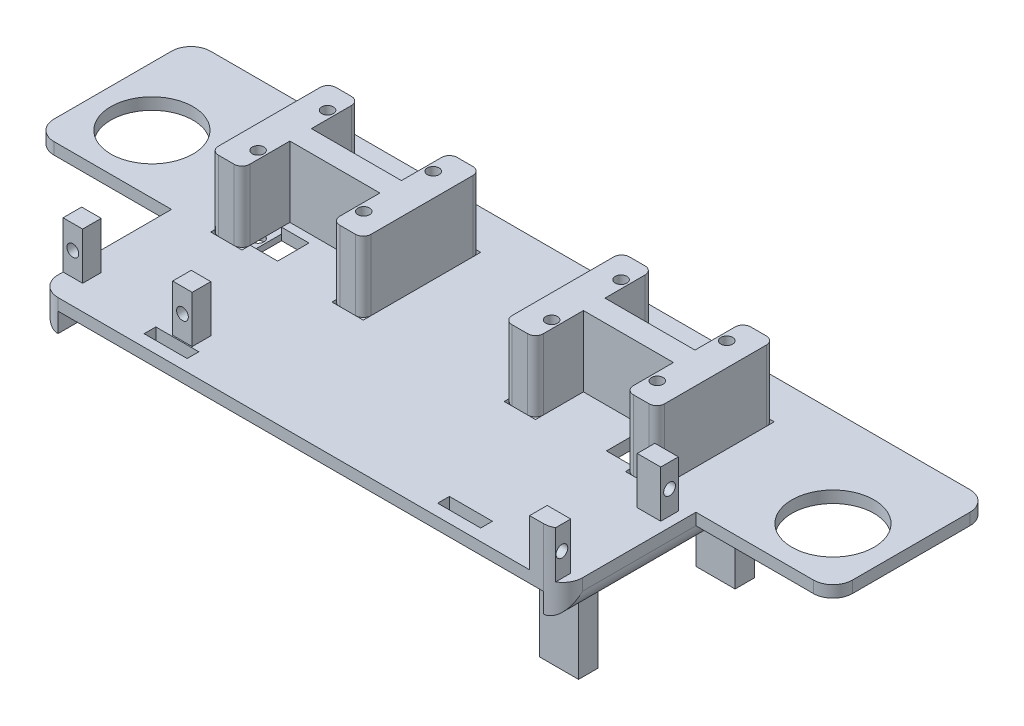
SolidWorks part; units mm, degrees
other "HMount1"
other "Controller Base"
other "HMount2"
ref_plane "Front Plane" through (0, 0, 0) normal (0, 0, 1) x (1, 0, 0)
ref_plane "Top Plane" through (0, 0, 0) normal (0, 1, 0) x (1, 0, 0)
ref_plane "Right Plane" through (0, 0, 0) normal (1, 0, 0) x (0, 0, -1)
sketch "Sketch1" plane through (0, 0, 0) normal (1, 0, 0) x (0, 0, -1)
  line L0 (0, 0) -> (0, 30)
  line L1 (0, 30) -> (45, 30)
  line L2 (45, 30) -> (45, 0)
  line L3 (45, 0) -> (40, 0)
  line L4 (40, 0) -> (40, 27)
  line L5 (40, 27) -> (5, 27)
  line L6 (5, 27) -> (5, 0)
  line L7 (5, 0) -> (0, 0)
  dimension "D1" = 5
  dimension "D2" = 5
  dimension "D3" = 3
  dimension "D4" = 35
  dimension "D5" = 30
extrude "C Bracket" add sketch "Sketch1" along normal blind 10
sketch "Sketch3" plane through (0, 30, 0) normal (0, 1, 0) x (1, 0, 0)
  line L0 (10, 45) -> (10, 0) construction
  line L1 (-113, -15) -> (21, -15)
  line L2 (-113, -15) -> (-113, 59)
  line L3 (-113, 59) -> (21, 59)
  line L4 (21, -15) -> (21, 59)
  line L5 (10, 0) -> (0, 0) construction
  line L6 (-148, 19) -> (-148, 59)
  line L7 (-113, 59) -> (-148, 59)
  line L8 (-46, 59) -> (-46, -15) construction
  line L9 (-113, 19) -> (-113, 59)
  line L10 (21, 19) -> (56, 19)
  line L11 (21, 19) -> (21, 59)
  line L12 (21, 59) -> (56, 59)
  line L13 (56, 19) -> (56, 59)
  line L14 (-113, 19) -> (-148, 19)
  line L15 (-113, -15) -> (-113, 59)
  circle A0 centre (41, 34) radius 10.5
  circle A1 centre (-133, 34) radius 10.5
  line M10 (0, 45) -> (0, 0)
  line M11 (0, 0) -> (10, 0)
  line M12 (10, 0) -> (10, 45)
  line M13 (10, 45) -> (0, 45)
  dimension "D9" = 21
  dimension "D1" = 74
  dimension "D2" = 134
  dimension "D3" = 11
  dimension "D4" = 15
  dimension "D5" = 25
  dimension "D6" = 20
  dimension "D7" = 35
  dimension "D8" = 40
extrude "Main Body" add sketch "Sketch3" along normal blind 3 separate body contours L8 L3 L2 L1 | L14 L2 L7 L6 A1 | L3 L8 L1 L4 M10 M13 M12 M11 | L10 L13 L12 L4 A0 | L2 L1 L4 L3 region at (-79.5, 30, -22) region at (-14.2469, 30, -21.9501) region at (-130.5, 30, -19.5315) region at (21.5315, 30, -39)
sketch "Sketch4" plane through (0, 30, 0) normal (0, -1, 0) x (1, 0, 0)
  line L0 (-148, -59) -> (56, -59) construction
  line L1 (-113, 15) -> (-108, 15)
  line L2 (-113, 15) -> (-113, -59)
  line L3 (-113, -59) -> (-108, -59)
  line L4 (-108, 15) -> (-108, -59)
  line L5 (-46, 15) -> (-46, -59) construction
  line L6 (-113, 15) -> (21, 15) construction
  line L7 (16, 15) -> (16, -59)
  line L8 (21, -59) -> (16, -59)
  line L9 (21, 15) -> (21, -59)
  line L10 (21, 15) -> (16, 15)
  dimension "D1" = 5
extrude "Boss-Extrude4" add sketch "Sketch4" along normal blind 5
sketch "Sketch6" plane through (0, 30, 0) normal (0, -1, 0) x (1, 0, 0)
  line L0 (0, -45) -> (0, 0) construction
  line L1 (10, -45) -> (0, -45) construction
  line L2 (10, -45) -> (10, 0) construction
  line L3 (10, 0) -> (0, 0) construction
  line L4 (0, -45) -> (0, 0)
  line L5 (10, -45) -> (0, -45)
  line L6 (10, -45) -> (10, 0)
  line L7 (10, 0) -> (0, 0)
extrude "C Bracket Insert" cut sketch "Sketch6" against normal blind 1.5
sketch "Sketch5" plane through (0, 33, 0) normal (0, 1, 0) x (1, 0, 0)
  line L0 (41, 34) -> (-133, 34) construction
  line L1 (-46, 59) -> (-46, -15) construction
  line L2 (-148, 59) -> (56, 59) construction
  line L3 (-113, -15) -> (21, -15) construction
  line L4 (-8.5, 36.75) -> (-8.5, 31.25) construction
  line L5 (-20, 31.25) -> (3, 31.25)
  line L7 (-20, 36.75) -> (3, 36.75)
  line L9 (3, 19) -> (3, 31.25)
  line L10 (-20, 19) -> (-28, 19)
  line L11 (-20, 19) -> (-20, 31.25)
  line L12 (-20, 49) -> (-28, 49)
  line L13 (-28, 19) -> (-28, 49)
  line L14 (11, 19) -> (11, 49)
  line L15 (3, 49) -> (11, 49)
  line L16 (3, 19) -> (11, 19)
  line L17 (-20, 36.75) -> (-20, 49)
  line L18 (3, 36.75) -> (3, 49)
  line L19 (-15.74, 36.75) -> (-15.74, 34) construction
  line L20 (-14.5781, 34) -> (-14.5781, 31.25) construction
  line L21 (-77.4219, 34) -> (-77.4219, 31.25) construction
  line L22 (-76.26, 36.75) -> (-76.26, 34) construction
  line L23 (-83.5, 36.75) -> (-83.5, 31.25) construction
  line L24 (-95, 36.75) -> (-95, 49)
  line L25 (-72, 36.75) -> (-72, 49)
  line L26 (-95, 19) -> (-103, 19)
  line L27 (-95, 49) -> (-103, 49)
  line L28 (-103, 19) -> (-103, 49)
  line L29 (-64, 19) -> (-64, 49)
  line L30 (-72, 49) -> (-64, 49)
  line L31 (-72, 19) -> (-72, 31.25)
  line L32 (-72, 19) -> (-64, 19)
  line L33 (-95, 19) -> (-95, 31.25)
  line L34 (-72, 36.75) -> (-95, 36.75)
  line L35 (-72, 31.25) -> (-95, 31.25)
  circle A0 centre (41, 34) radius 10.5 construction
  circle A1 centre (41, 34) radius 10.5
  point P22 (-28, 34)
  dimension "D1" = 5.5
  dimension "D2" = 23
  dimension "D3" = 30
  dimension "D4" = 8
  dimension "D5" = 30
extrude "Motor Holders" add sketch "Sketch5" along normal blind 18 separate body contours L24 L27 L28 L26 L33 L35 L31 L32 L29 L30 L25 L34 | L5 L9 L16 L14 L15 L18 L7 L17 L12 L13 L10 L11
sketch "Sketch11" plane through (0, 33, 0) normal (0, 1, 0) x (1, 0, 0)
  line L0 (-20, 36.75) -> (-20, 49) construction
  line L1 (-20, 49) -> (-28, 49) construction
  line L2 (-28, 19) -> (-28, 49) construction
  line L3 (-20, 19) -> (-28, 19) construction
  line L4 (-20, 19) -> (-20, 31.25) construction
  line L5 (-20, 31.25) -> (3, 31.25) construction
  line L6 (-20, 36.75) -> (3, 36.75) construction
  line L7 (3, 36.75) -> (3, 49) construction
  line L8 (3, 19) -> (3, 31.25) construction
  line L9 (3, 19) -> (11, 19) construction
  line L10 (11, 19) -> (11, 49) construction
  line L11 (3, 49) -> (11, 49) construction
  line L12 (-72, 19) -> (-72, 31.25) construction
  line L13 (-72, 19) -> (-64, 19) construction
  line L14 (-64, 19) -> (-64, 49) construction
  line L15 (-72, 49) -> (-64, 49) construction
  line L16 (-72, 36.75) -> (-72, 49) construction
  line L17 (-72, 36.75) -> (-95, 36.75) construction
  line L18 (-72, 31.25) -> (-95, 31.25) construction
  line L19 (-95, 19) -> (-103, 19) construction
  line L20 (-95, 19) -> (-95, 31.25) construction
  line L21 (-95, 36.75) -> (-95, 49) construction
  line L22 (-95, 49) -> (-103, 49) construction
  line L23 (-103, 19) -> (-103, 49) construction
  line L24 (-20, 36.75) -> (-20, 49)
  line L25 (-20, 49) -> (-28, 49)
  line L26 (-28, 19) -> (-28, 49)
  line L27 (-20, 19) -> (-28, 19)
  line L28 (-20, 19) -> (-20, 31.25)
  line L29 (-20, 31.25) -> (3, 31.25)
  line L30 (-20, 36.75) -> (3, 36.75)
  line L31 (3, 36.75) -> (3, 49)
  line L32 (3, 19) -> (3, 31.25)
  line L33 (3, 19) -> (11, 19)
  line L34 (11, 19) -> (11, 49)
  line L35 (3, 49) -> (11, 49)
  line L36 (-72, 19) -> (-72, 31.25)
  line L37 (-72, 19) -> (-64, 19)
  line L38 (-64, 19) -> (-64, 49)
  line L39 (-72, 49) -> (-64, 49)
  line L40 (-72, 36.75) -> (-72, 49)
  line L41 (-72, 36.75) -> (-95, 36.75)
  line L42 (-72, 31.25) -> (-95, 31.25)
  line L43 (-95, 19) -> (-103, 19)
  line L44 (-95, 19) -> (-95, 31.25)
  line L45 (-95, 36.75) -> (-95, 49)
  line L46 (-95, 49) -> (-103, 49)
  line L47 (-103, 19) -> (-103, 49)
extrude "Motor Holder Insert" cut sketch "Sketch11" against normal blind 1.5
sketch "Sketch12" plane through (0, 51, 0) normal (0, 1, 0) x (1, 0, 0)
  line L0 (3, 42.875) -> (11, 42.875) construction
  line L1 (3, 49) -> (3, 36.75) construction
  line L2 (11, 19) -> (11, 49) construction
  line L3 (-4, 21.125) -> (3, 29.125) construction
  line L8 (-8.5, 36.75) -> (-8.5, 59) construction
  line L9 (-20, 36.75) -> (3, 36.75) construction
  line L10 (-148, 59) -> (56, 59) construction
  line L11 (3, 36.75) -> (3, 49) construction
  line L12 (-4, 38.875) -> (3, 38.875)
  line L13 (-4, 38.875) -> (-4, 46.875)
  line L14 (-4, 46.875) -> (3, 46.875)
  line L15 (3, 38.875) -> (3, 46.875)
  line L16 (-4, 38.875) -> (3, 46.875) construction
  line L17 (-4, 46.875) -> (3, 38.875) construction
  line L18 (-28, 34) -> (11, 34) construction
  line L19 (-14, 53) -> (-3, 53)
  line L20 (-14, 53) -> (-14, 56)
  line L21 (-14, 56) -> (-3, 56)
  line L22 (-3, 53) -> (-3, 56)
  line L23 (-14, 53) -> (-3, 56) construction
  line L24 (-14, 56) -> (-3, 53) construction
  line L25 (-28, 19) -> (-28, 49) construction
  line L26 (11, 19) -> (11, 49) construction
  line L27 (-46, 59) -> (-46, -15) construction
  line L28 (-113, -15) -> (21, -15) construction
  line L29 (21, -15) -> (21, 59) construction
  line L30 (21, 22) -> (-114.2213, 22) construction
  line L31 (-4, 29.125) -> (3, 21.125) construction
  line L32 (3, 25.125) -> (11, 25.125) construction
  line L33 (3, 29.125) -> (3, 21.125)
  line L34 (-4, 21.125) -> (3, 21.125)
  line L35 (-4, 29.125) -> (-4, 21.125)
  line L36 (-4, 29.125) -> (3, 29.125)
  line L37 (-14, -12) -> (-3, -9) construction
  line L38 (-14, -9) -> (-3, -12) construction
  line L39 (-3, -9) -> (-3, -12)
  line L40 (-14, -12) -> (-3, -12)
  line L41 (-14, -9) -> (-14, -12)
  line L42 (-14, -9) -> (-3, -9)
  line L43 (-78, -9) -> (-89, -12) construction
  line L44 (-78, -12) -> (-89, -9) construction
  line L45 (-95, 25.125) -> (-103, 25.125) construction
  line L46 (-88, 29.125) -> (-95, 21.125) construction
  line L47 (-113, -15) -> (-113, 59) construction
  line L48 (-78, 56) -> (-89, 53) construction
  line L49 (-78, 53) -> (-89, 56) construction
  line L50 (-64, 34) -> (-103, 34) construction
  line L51 (-88, 46.875) -> (-95, 38.875) construction
  line L52 (-88, 38.875) -> (-95, 46.875) construction
  line L53 (-83.5, 36.75) -> (-83.5, 59) construction
  line L54 (-88, 21.125) -> (-95, 29.125) construction
  line L55 (-95, 42.875) -> (-103, 42.875) construction
  line L56 (-78, -9) -> (-89, -9)
  line L57 (-78, -9) -> (-78, -12)
  line L58 (-78, -12) -> (-89, -12)
  line L59 (-89, -9) -> (-89, -12)
  line L60 (-88, 29.125) -> (-95, 29.125)
  line L61 (-88, 29.125) -> (-88, 21.125)
  line L62 (-88, 21.125) -> (-95, 21.125)
  line L63 (-95, 29.125) -> (-95, 21.125)
  line L64 (-89, 53) -> (-89, 56)
  line L65 (-78, 56) -> (-89, 56)
  line L66 (-78, 53) -> (-78, 56)
  line L67 (-78, 53) -> (-89, 53)
  line L68 (-95, 38.875) -> (-95, 46.875)
  line L69 (-88, 46.875) -> (-95, 46.875)
  line L70 (-88, 38.875) -> (-88, 46.875)
  line L71 (-88, 38.875) -> (-95, 38.875)
  line L72 (-103, 19) -> (-103, 49) construction
  line L73 (-103, 38) -> (-108, 38)
  line L74 (-103, 38) -> (-103, 30)
  line L75 (-103, 30) -> (-108, 30)
  line L76 (-108, 38) -> (-108, 30)
  line L77 (-28, 49) -> (-28, 19) construction
  line L78 (-28, 30) -> (-33, 30)
  line L79 (-28, 30) -> (-28, 38)
  line L80 (-28, 38) -> (-33, 38)
  line L81 (-33, 30) -> (-33, 38)
  circle A0 centre (5, 42.875) radius 1.5
  circle A1 centre (5, 25.125) radius 1.5
  circle A2 centre (-22, 25.125) radius 1.5
  circle A3 centre (-22, 42.875) radius 1.5
  circle A4 centre (-70, 42.875) radius 1.5
  circle A5 centre (-70, 25.125) radius 1.5
  circle A6 centre (-97, 25.125) radius 1.5
  circle A7 centre (-97, 42.875) radius 1.5
  point P6 (-0.5, 42.875)
  point P20 (-8.5, 54.5)
  point P50 (-0.5, 25.125)
  point P59 (-8.5, -10.5)
  point P94 (-83.5, -10.5)
  point P95 (-91.5, 25.125)
  point P96 (-83.5, 54.5)
  point P97 (-91.5, 42.875)
  point P104 (-103, 34)
  point P111 (-28, 34)
  dimension "D6" = 3
  dimension "D1" = 3
  dimension "D2" = 3
  dimension "D3" = 11
  dimension "D4" = 7
  dimension "D5" = 8
  dimension "D7" = 2
  dimension "D8" = 5
  dimension "D9" = 8
  dimension "D10" = 5
  dimension "D11" = 8
extrude "Strap and Screw Holes" cut sketch "Sketch12" against normal up to surface (21 mm away) up to face at (-133, 30, -23.5)
sketch "Sketch13" plane through (0, 33, 0) normal (0, 1, 0) x (1, 0, 0)
  line L0 (-113, -15) -> (21, -15) construction
  line L1 (18.5, -15) -> (12.5, -15)
  line L2 (18.5, -15) -> (18.5, -10.5)
  line L3 (18.5, -10.5) -> (12.5, -10.5)
  line L4 (12.5, -15) -> (12.5, -10.5)
  line L5 (21, -15) -> (21, 19) construction
  line L6 (18.5, 12.5) -> (12.5, 12.5)
  line L7 (18.5, 12.5) -> (18.5, 17)
  line L8 (18.5, 17) -> (12.5, 17)
  line L9 (12.5, 12.5) -> (12.5, 17)
  dimension "D1" = 2.5
  dimension "D2" = 6
  dimension "D3" = 4.5
  dimension "D4" = 6
  dimension "D5" = 2.5
  dimension "D6" = 23
  dimension "D7" = 4.5
extrude "Boss-Extrude8" add sketch "Sketch13" along normal blind 12
sketch "Sketch14" plane through (18.5, 0, 0) normal (1, 0, 0) x (0, 0, -1)
  line L0 (-12.75, 45) -> (-12.75, 33) construction
  line L1 (-15, 45) -> (-10.5, 45) construction
  line L2 (-15, 33) -> (-10.5, 33) construction
  line L3 (14.75, 45) -> (14.75, 33) construction
  line L4 (12.5, 45) -> (17, 45) construction
  line L5 (12.5, 33) -> (17, 33) construction
  circle A0 centre (-12.75, 39) radius 1.5
  circle A1 centre (14.75, 39) radius 1.5
  dimension "D3" = 3
  dimension "D1" = 6
  dimension "D2" = 6
extrude "Cut-Extrude6" cut sketch "Sketch14" against normal up to surface (6 mm away) up to face at (12.5, 39, 12.75)
sketch "Sketch15" plane through (0, 33, 0) normal (0, 1, 0) x (1, 0, 0)
  line L1 (-108, -8.7) -> (-113, -8.7)
  line L2 (-108, -8.7) -> (-108, -3.95)
  line L3 (-108, -3.95) -> (-113, -3.95)
  line L4 (-113, -8.7) -> (-113, -3.95)
  line L5 (-108, -8.7) -> (-113, -3.95) construction
  line L6 (-108, -3.95) -> (-113, -8.7) construction
  line L7 (-80, -8.7) -> (-85, -8.7)
  line L8 (-80, -8.7) -> (-80, -3.95)
  line L9 (-80, -3.95) -> (-85, -3.95)
  line L10 (-85, -8.7) -> (-85, -3.95)
  line L11 (-80, -8.7) -> (-85, -3.95) construction
  line L12 (-80, -3.95) -> (-85, -8.7) construction
  line L13 (-113, -15) -> (12.5, -15) construction
  line L14 (-113, -15) -> (-113, 19) construction
  point P0 (-110.5, -6.325)
  point P5 (-82.5, -6.325)
  dimension "D1" = 23
  dimension "D2" = 4.75
  dimension "D3" = 5
  dimension "D4" = 6.3
extrude "Boss-Extrude9" add sketch "Sketch15" along normal blind 12
sketch "Sketch16" plane through (0, 0, 8.7) normal (0, 0, 1) x (1, 0, 0)
  line L0 (-110.5, 45) -> (-110.5, 33) construction
  line L1 (-113, 45) -> (-108, 45) construction
  line L2 (-113, 33) -> (-108, 33) construction
  line L3 (-82.5, 45) -> (-82.5, 33) construction
  line L4 (-85, 45) -> (-80, 45) construction
  line L5 (-113, 33) -> (12.5, 33) construction
  line L6 (-85, 33) -> (-80, 33) construction
  circle A0 centre (-110.5, 39) radius 1.5
  circle A1 centre (-82.5, 39) radius 1.5
  dimension "D3" = 3
  dimension "D1" = 6
  dimension "D2" = 6
extrude "Cut-Extrude7" cut sketch "Sketch16" against normal up to surface (4.75 mm away) up to face at (-110.5, 39, 3.95)
fillet "Fillet1" radius 5 8 edges at (-113, 25, -22) (21, 25, -22) (21, 29, 15) (-113, 29, 15) (56, 31.5, -19) (56, 31.5, -59) (-148, 31.5, -19) (-148, 31.5, -59)
fillet "Fillet2" radius 2 8 edges at (-72, 42, -19) (-64, 42, -19) (-64, 42, -49) (-72, 42, -49) (-95, 42, -49) (-103, 42, -49) (-95, 42, -19) (-103, 42, -19)
fillet "Fillet3" radius 2 8 edges at (3, 42, -19) (11, 42, -19) (3, 42, -49) (11, 42, -49) (-28, 42, -49) (-20, 42, -49) (-20, 42, -19) (-28, 42, -19)
sketch "Sketch17" plane through (0, 30, 0) normal (0, -1, 0) x (1, 0, 0)
  line L0 (-108, -22) -> (16, -22) construction
  line L1 (-108, -59) -> (-108, 15) construction
  line L2 (16, 15) -> (16, -59) construction
  line L3 (-46, -22) -> (-46, 15) construction
  line L4 (-66, -27) -> (-26, -27)
  line L5 (-66, -27) -> (-66, -17)
  line L6 (-66, -17) -> (-26, -17)
  line L7 (-26, -27) -> (-26, -17)
  line L8 (-66, -27) -> (-26, -17) construction
  line L9 (-66, -17) -> (-26, -27) construction
  line L10 (-108, 15) -> (16, 15) construction
  line L11 (-46, -3.5) -> (-108, -3.5) construction
  line L13 (-108, -8.5) -> (-68, -8.5)
  line L14 (-108, -8.5) -> (-108, 1.5)
  line L15 (-108, 1.5) -> (-68, 1.5)
  line L16 (-68, -8.5) -> (-68, 1.5)
  line L17 (-108, -8.5) -> (-68, 1.5) construction
  line L18 (-108, 1.5) -> (-68, -8.5) construction
  point P6 (-46, -22)
  point P17 (-88, -3.5)
  dimension "D1" = 40
  dimension "D2" = 10
  dimension "D3" = 10
  dimension "D4" = 40
extrude "Boss-Extrude11" add sketch "Sketch17" along normal blind 5
